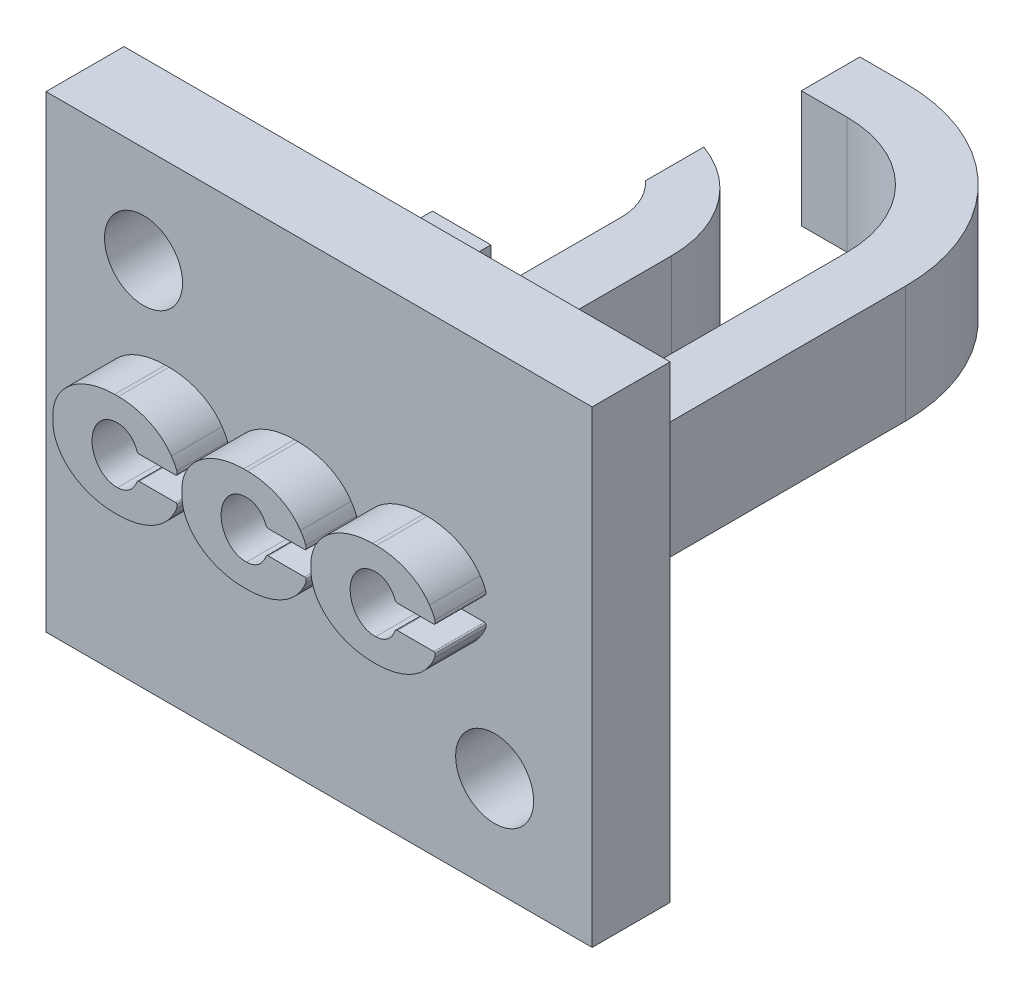
SolidWorks part; units mm, degrees
ref_plane "Front Plane" through (0, 0, 0) normal (0, 0, 1) x (1, 0, 0)
ref_plane "Top Plane" through (0, 0, 0) normal (0, 1, 0) x (1, 0, 0)
ref_plane "Right Plane" through (0, 0, 0) normal (1, 0, 0) x (0, 0, -1)
sketch "Sketch1" plane through (0, 0, 0) normal (0, 0, 1) x (1, 0, 0)
  line L1 (-7.5, 6) -> (7.5, 6)
  line L2 (-7.5, 6) -> (-7.5, -6)
  line L3 (-7.5, -6) -> (7.5, -6)
  line L4 (7.5, 6) -> (7.5, -6)
  line L5 (-7.5, 6) -> (7.5, -6) construction
  line L6 (-7.5, -6) -> (7.5, 6) construction
  point P0 (0, 0)
  dimension "D1" = 15
  dimension "D2" = 12
extrude "Boss-Extrude1" add sketch "Sketch1" along normal blind 2
sketch "Sketch2" plane through (0, 0, 2) normal (0, 0, 1) x (1, 0, 0)
  line L0 (-0.5005, 0.4472) -> (0.4353, 0.4472)
  line L1 (-1.0379, 1.458) -> (-1.1315, 1.458)
  line L2 (-2.7171, 0.2068) -> (-2.7171, 0.0767)
  line L3 (-1.1315, -1.1745) -> (-1.0379, -1.1745)
  line L4 (0.4308, -0.1598) -> (-0.5005, -0.1598)
  line L5 (-3.8088, 0.4472) -> (-2.873, 0.4472)
  line L6 (-4.3462, 1.458) -> (-4.4398, 1.458)
  line L7 (-6.0254, 0.2068) -> (-6.0254, 0.0767)
  line L8 (-4.4398, -1.1745) -> (-4.3462, -1.1745)
  line L9 (-2.8775, -0.1598) -> (-3.8088, -0.1598)
  line L10 (2.8078, 0.4472) -> (3.7437, 0.4472)
  line L11 (2.2704, 1.458) -> (2.1768, 1.458)
  line L12 (0.5912, 0.2068) -> (0.5912, 0.0767)
  line L13 (2.1768, -1.1745) -> (2.2704, -1.1745)
  line L14 (3.7391, -0.1598) -> (2.8078, -0.1598)
  arc A0 (-0.5622, 0.4908) -> (-0.5005, 0.4472) centre (-0.5005, 0.5126) ccw
  arc A1 (0.4353, 0.4472) -> (0.4646, 0.4721) centre (0.4309, 0.4821) ccw
  arc A2 (0.4646, 0.4721) -> (0.4604, 0.5595) centre (0.284, 0.5073) ccw
  arc A3 (0.4604, 0.5595) -> (0.3232, 0.8168) centre (-0.6216, 0.148) ccw
  arc A4 (0.3232, -0.5333) -> (0.4557, -0.287) centre (-0.6122, 0.1283) ccw
  arc A5 (0.4557, -0.287) -> (0.4655, -0.189) centre (0.2842, -0.2203) ccw
  arc A6 (0.4655, -0.189) -> (0.4308, -0.1598) centre (0.4308, -0.195) ccw
  arc A7 (-0.5005, -0.1598) -> (-0.5622, -0.2034) centre (-0.5005, -0.2253) ccw
  arc A8 (-3.8705, 0.4908) -> (-3.8088, 0.4472) centre (-3.8088, 0.5126) ccw
  arc A9 (-2.873, 0.4472) -> (-2.8437, 0.4721) centre (-2.8774, 0.4821) ccw
  arc A10 (-2.8437, 0.4721) -> (-2.8479, 0.5595) centre (-3.0243, 0.5073) ccw
  arc A11 (-2.8479, 0.5595) -> (-2.9851, 0.8168) centre (-3.9299, 0.148) ccw
  arc A12 (-2.9851, -0.5333) -> (-2.8527, -0.287) centre (-3.9205, 0.1283) ccw
  arc A13 (-2.8527, -0.287) -> (-2.8428, -0.189) centre (-3.0241, -0.2203) ccw
  arc A14 (-2.8428, -0.189) -> (-2.8775, -0.1598) centre (-2.8775, -0.195) ccw
  arc A15 (-3.8088, -0.1598) -> (-3.8705, -0.2034) centre (-3.8088, -0.2253) ccw
  arc A16 (2.7461, 0.4908) -> (2.8078, 0.4472) centre (2.8078, 0.5126) ccw
  arc A17 (3.7437, 0.4472) -> (3.7729, 0.4721) centre (3.7392, 0.4821) ccw
  arc A18 (3.7729, 0.4721) -> (3.7687, 0.5595) centre (3.5923, 0.5073) ccw
  arc A19 (3.7687, 0.5595) -> (3.6315, 0.8168) centre (2.6867, 0.148) ccw
  arc A20 (3.6315, -0.5333) -> (3.764, -0.287) centre (2.6961, 0.1283) ccw
  arc A21 (3.764, -0.287) -> (3.7738, -0.189) centre (3.5925, -0.2203) ccw
  arc A22 (3.7738, -0.189) -> (3.7391, -0.1598) centre (3.7391, -0.195) ccw
  arc A23 (2.8078, -0.1598) -> (2.7461, -0.2034) centre (2.8078, -0.2253) ccw
  ellipse E0 centre (-1.0904, 0.1419) end of major axis (-1.0868, -0.5752) minor radius 0.6209 (-1.1185, 0.8583) -> (-1.0587, -0.5743) ccw
  ellipse E1 centre (-1.1465, 0.1419) end of major axis (-1.4291, -0.5397) minor radius 0.6039 (-0.5622, 0.4908) -> (-1.1185, 0.8583) ccw
  ellipse E2 centre (-1.1599, 0.1563) end of major axis (0.4829, 0.4015) minor radius 1.2925 (0.3232, 0.8168) -> (-1.0379, 1.458) ccw
  ellipse E3 centre (-1.0691, 0.1576) end of major axis (-2.714, 0.287) minor radius 1.2979 (-1.1315, 1.458) -> (-2.7171, 0.2068) ccw
  ellipse E4 centre (-1.0691, 0.1259) end of major axis (0.5758, 0.2553) minor radius 1.2979 (-2.7171, 0.0767) -> (-1.1315, -1.1745) ccw
  ellipse E5 centre (-1.1599, 0.1272) end of major axis (-2.8027, 0.3723) minor radius 1.2925 (-1.0379, -1.1745) -> (0.3232, -0.5333) ccw
  ellipse E6 centre (-1.1465, 0.1455) end of major axis (-0.8639, -0.5361) minor radius 0.6039 (-1.0587, -0.5743) -> (-0.5622, -0.2034) ccw
  ellipse E7 centre (-4.4548, 0.1419) end of major axis (-4.1722, 0.8235) minor radius 0.6039 (-3.8705, 0.4908) -> (-4.4268, 0.8583) ccw
  ellipse E8 centre (-4.4682, 0.1563) end of major axis (-2.8254, 0.4015) minor radius 1.2925 (-2.9851, 0.8168) -> (-4.3462, 1.458) ccw
  ellipse E9 centre (-4.3774, 0.1576) end of major axis (-6.0223, 0.287) minor radius 1.2979 (-4.4398, 1.458) -> (-6.0254, 0.2068) ccw
  ellipse E10 centre (-4.3774, 0.1259) end of major axis (-6.0223, -0.0034) minor radius 1.2979 (-6.0254, 0.0767) -> (-4.4398, -1.1745) ccw
  ellipse E11 centre (-4.4682, 0.1272) end of major axis (-6.111, 0.3723) minor radius 1.2925 (-4.3462, -1.1745) -> (-2.9851, -0.5333) ccw
  ellipse E12 centre (-4.4548, 0.1455) end of major axis (-4.7375, 0.8271) minor radius 0.6039 (-4.367, -0.5743) -> (-3.8705, -0.2034) ccw
  ellipse E13 centre (-4.3987, 0.1419) end of major axis (-4.3951, -0.5752) minor radius 0.6209 (-4.4268, 0.8583) -> (-4.367, -0.5743) ccw
  ellipse E14 centre (2.2179, 0.1419) end of major axis (2.2143, 0.859) minor radius 0.6209 (2.1899, 0.8583) -> (2.2496, -0.5743) ccw
  ellipse E15 centre (2.1618, 0.1419) end of major axis (1.8792, -0.5397) minor radius 0.6039 (2.7461, 0.4908) -> (2.1899, 0.8583) ccw
  ellipse E16 centre (2.1484, 0.1563) end of major axis (3.7912, 0.4015) minor radius 1.2925 (3.6315, 0.8168) -> (2.2704, 1.458) ccw
  ellipse E17 centre (2.2392, 0.1576) end of major axis (0.5943, 0.287) minor radius 1.2979 (2.1768, 1.458) -> (0.5912, 0.2068) ccw
  ellipse E18 centre (2.2392, 0.1259) end of major axis (3.8841, 0.2553) minor radius 1.2979 (0.5912, 0.0767) -> (2.1768, -1.1745) ccw
  ellipse E19 centre (2.1484, 0.1272) end of major axis (0.5056, 0.3723) minor radius 1.2925 (2.2704, -1.1745) -> (3.6315, -0.5333) ccw
  ellipse E20 centre (2.1618, 0.1455) end of major axis (1.8792, 0.8271) minor radius 0.6039 (2.2496, -0.5743) -> (2.7461, -0.2034) ccw
extrude "Boss-Extrude2" add sketch "Sketch2" along normal blind 2
sketch "Sketch3" plane through (0, 0, 0) normal (0, 1, 0) x (1, 0, 0)
  line L0 (7.5, 0) -> (-7.5, 0) construction
  line L1 (1.8337, 0) -> (3.3337, 0)
  line L2 (1.8337, 0) -> (1.8337, 12.2)
  line L3 (-3.644, -2) -> (-3.644, 5.3789) construction
  line L4 (3.3337, 0) -> (3.3337, 13.7)
  line L5 (-4.394, 0) -> (-2.894, 0)
  line L6 (-4.394, 0) -> (-4.394, 4.8)
  line L7 (-1.0877, -2) -> (-1.0877, 4.6797) construction
  line L8 (-2.894, 0) -> (-2.894, 4.8)
  line L9 (-2.894, 4.8) -> (-4.394, 4.8)
  line L10 (-1.8377, 0) -> (-0.3377, 0)
  line L11 (7.5, -2) -> (-7.5, -2) construction
  line L13 (-1.8377, 0) -> (-1.8377, 8.2)
  line L14 (2.5837, -2) -> (2.5837, 2.787) construction
  line L15 (-0.3377, 0) -> (-0.3377, 9.7)
  line L16 (-0.3377, 9.7) -> (-2.3377, 9.7)
  line L17 (-2.3377, 13.7) -> (3.3337, 13.7)
  line L18 (-1.8377, 8.2) -> (-2.3377, 8.2)
  line L19 (-2.3377, 9.7) -> (-2.3377, 8.2)
  line L20 (-2.3377, 13.7) -> (-2.3377, 12.2)
  line L21 (-2.3377, 12.2) -> (1.8337, 12.2)
  dimension "D1" = 1.5
  dimension "D2" = 4.8
  dimension "D3" = 1.5
  dimension "D4" = 1.5
  dimension "D5" = 8.2
  dimension "D6" = 1.5
  dimension "D7" = 2.5
  dimension "D8" = 1.5
  dimension "D9" = 0.5
  dimension "D10" = 1.0877
  dimension "D11" = 2.5837
  dimension "D12" = 3.644
extrude "Boss-Extrude3" add sketch "Sketch3" along normal mid plane 3
fillet "Fillet3" radius 1.5 1 edges at (-1.8377, 0, -8.2)
fillet "Fillet4" radius 3 1 edges at (-0.3377, 0, -9.7)
fillet "Fillet5" radius 3 1 edges at (1.8337, 0, -12.2)
fillet "Fillet6" radius 4.5 1 edges at (3.3337, 0, -13.7)
sketch "Sketch4" plane through (7.5, 0, 0) normal (1, 0, 0) x (0, 0, -1)
  line L4 (0, -6) -> (0, 6)
  line L5 (0, 6) -> (-2, 6)
  line L6 (-2, 6) -> (-2, -6)
  line L7 (-2, -6) -> (0, -6)
  line L8 (0, -6) -> (0, 6)
  line L9 (0, 6) -> (-2, 6)
  line L10 (-2, 6) -> (-2, -6)
  line L11 (-2, -6) -> (0, -6)
  dimension "D1" = 0
extrude "Cut-Extrude1" cut sketch "Sketch4" against normal blind 1
sketch "Sketch5" plane through (0, 0, 0) normal (0, 0, -1) x (-1, 0, 0)
  line L0 (-6.5, -6) -> (-6.5, 6) construction
  line L1 (7.5, -6) -> (-6.5, -6) construction
  line L2 (7.5, 6) -> (7.5, -6) construction
  line L3 (-6.5, 6) -> (7.5, 6) construction
  circle A0 centre (-4, -3.5) radius 1
  circle A1 centre (5, 3.5) radius 1
  dimension "D1" = 2
  dimension "D2" = 2.5
  dimension "D3" = 2.5
  dimension "D4" = 2.5
  dimension "D5" = 2.5
extrude "Cut-Extrude2" cut sketch "Sketch5" against normal through all
sketch "Sketch6" plane through (0, 0, 4) normal (0, 0, 1) x (1, 0, 0)
  line L0 (-0.5005, 0.4472) -> (0.4353, 0.4472) construction
  line L1 (-1.0379, 1.458) -> (-1.1315, 1.458) construction
  line L2 (-2.7171, 0.2068) -> (-2.7171, 0.0767) construction
  line L3 (-1.1315, -1.1745) -> (-1.0379, -1.1745) construction
  line L4 (0.4308, -0.1598) -> (-0.5005, -0.1598) construction
  line L5 (-3.8088, 0.4472) -> (-2.873, 0.4472)
  line L6 (-4.3462, 1.458) -> (-4.4398, 1.458)
  line L7 (-6.0254, 0.2068) -> (-6.0254, 0.0767)
  line L8 (-4.4398, -1.1745) -> (-4.3462, -1.1745)
  line L9 (-2.8775, -0.1598) -> (-3.8088, -0.1598)
  line L10 (-3.8088, 0.4472) -> (-2.873, 0.4472)
  line L11 (-4.3462, 1.458) -> (-4.4398, 1.458)
  line L12 (-6.0254, 0.2068) -> (-6.0254, 0.0767)
  line L13 (-4.4398, -1.1745) -> (-4.3462, -1.1745)
  line L14 (-2.8775, -0.1598) -> (-3.8088, -0.1598)
  line L15 (2.8078, 0.4472) -> (3.7437, 0.4472) construction
  line L16 (2.2704, 1.458) -> (2.1768, 1.458) construction
  line L17 (0.5912, 0.2068) -> (0.5912, 0.0767) construction
  line L18 (2.1768, -1.1745) -> (2.2704, -1.1745) construction
  line L19 (3.7391, -0.1598) -> (2.8078, -0.1598) construction
  line L20 (-0.5005, 0.4472) -> (0.4353, 0.4472)
  line L21 (-1.0379, 1.458) -> (-1.1315, 1.458)
  line L22 (-2.7171, 0.2068) -> (-2.7171, 0.0767)
  line L23 (-1.1315, -1.1745) -> (-1.0379, -1.1745)
  line L24 (0.4308, -0.1598) -> (-0.5005, -0.1598)
  line L25 (2.8078, 0.4472) -> (3.7437, 0.4472)
  line L26 (2.2704, 1.458) -> (2.1768, 1.458)
  line L27 (0.5912, 0.2068) -> (0.5912, 0.0767)
  line L28 (2.1768, -1.1745) -> (2.2704, -1.1745)
  line L29 (3.7391, -0.1598) -> (2.8078, -0.1598)
  arc A0 (-0.5622, 0.4908) -> (-0.5005, 0.4472) centre (-0.5005, 0.5126) ccw construction
  arc A1 (0.4353, 0.4472) -> (0.4646, 0.4721) centre (0.4309, 0.4821) ccw construction
  arc A2 (0.4646, 0.4721) -> (0.4604, 0.5595) centre (0.284, 0.5073) ccw construction
  arc A3 (0.4604, 0.5595) -> (0.3232, 0.8168) centre (-0.6216, 0.148) ccw construction
  arc A4 (0.3232, -0.5333) -> (0.4557, -0.287) centre (-0.6122, 0.1283) ccw construction
  arc A5 (0.4557, -0.287) -> (0.4655, -0.189) centre (0.2842, -0.2203) ccw construction
  arc A6 (0.4655, -0.189) -> (0.4308, -0.1598) centre (0.4308, -0.195) ccw construction
  arc A7 (-0.5005, -0.1598) -> (-0.5622, -0.2034) centre (-0.5005, -0.2253) ccw construction
  arc A8 (-3.8705, 0.4908) -> (-3.8088, 0.4472) centre (-3.8088, 0.5126) ccw
  arc A9 (-2.873, 0.4472) -> (-2.8437, 0.4721) centre (-2.8774, 0.4821) ccw
  arc A10 (-2.8437, 0.4721) -> (-2.8479, 0.5595) centre (-3.0243, 0.5073) ccw
  arc A11 (-2.8479, 0.5595) -> (-2.9851, 0.8168) centre (-3.9299, 0.148) ccw
  arc A12 (-2.9851, -0.5333) -> (-2.8527, -0.287) centre (-3.9205, 0.1283) ccw
  arc A13 (-2.8527, -0.287) -> (-2.8428, -0.189) centre (-3.0241, -0.2203) ccw
  arc A14 (-2.8428, -0.189) -> (-2.8775, -0.1598) centre (-2.8775, -0.195) ccw
  arc A15 (-3.8088, -0.1598) -> (-3.8705, -0.2034) centre (-3.8088, -0.2253) ccw
  arc A16 (-3.8705, 0.4908) -> (-3.8088, 0.4472) centre (-3.8088, 0.5126) ccw
  arc A17 (-2.873, 0.4472) -> (-2.8437, 0.4721) centre (-2.8774, 0.4821) ccw
  arc A18 (-2.8437, 0.4721) -> (-2.8479, 0.5595) centre (-3.0243, 0.5073) ccw
  arc A19 (-2.8479, 0.5595) -> (-2.9851, 0.8168) centre (-3.9299, 0.148) ccw
  arc A20 (-2.9851, -0.5333) -> (-2.8527, -0.287) centre (-3.9205, 0.1283) ccw
  arc A21 (-2.8527, -0.287) -> (-2.8428, -0.189) centre (-3.0241, -0.2203) ccw
  arc A22 (-2.8428, -0.189) -> (-2.8775, -0.1598) centre (-2.8775, -0.195) ccw
  arc A23 (-3.8088, -0.1598) -> (-3.8705, -0.2034) centre (-3.8088, -0.2253) ccw
  arc A24 (2.7461, 0.4908) -> (2.8078, 0.4472) centre (2.8078, 0.5126) ccw construction
  arc A25 (3.7437, 0.4472) -> (3.7729, 0.4721) centre (3.7392, 0.4821) ccw construction
  arc A26 (3.7729, 0.4721) -> (3.7687, 0.5595) centre (3.5923, 0.5073) ccw construction
  arc A27 (3.7687, 0.5595) -> (3.6315, 0.8168) centre (2.6867, 0.148) ccw construction
  arc A28 (3.6315, -0.5333) -> (3.764, -0.287) centre (2.6961, 0.1283) ccw construction
  arc A29 (3.764, -0.287) -> (3.7738, -0.189) centre (3.5925, -0.2203) ccw construction
  arc A30 (3.7738, -0.189) -> (3.7391, -0.1598) centre (3.7391, -0.195) ccw construction
  arc A31 (2.8078, -0.1598) -> (2.7461, -0.2034) centre (2.8078, -0.2253) ccw construction
  arc A32 (-0.5622, 0.4908) -> (-0.5005, 0.4472) centre (-0.5005, 0.5126) ccw
  arc A33 (0.4353, 0.4472) -> (0.4646, 0.4721) centre (0.4309, 0.4821) ccw
  arc A34 (0.4646, 0.4721) -> (0.4604, 0.5595) centre (0.284, 0.5073) ccw
  arc A35 (0.4604, 0.5595) -> (0.3232, 0.8168) centre (-0.6216, 0.148) ccw
  arc A36 (0.3232, -0.5333) -> (0.4557, -0.287) centre (-0.6122, 0.1283) ccw
  arc A37 (0.4557, -0.287) -> (0.4655, -0.189) centre (0.2842, -0.2203) ccw
  arc A38 (0.4655, -0.189) -> (0.4308, -0.1598) centre (0.4308, -0.195) ccw
  arc A39 (-0.5005, -0.1598) -> (-0.5622, -0.2034) centre (-0.5005, -0.2253) ccw
  arc A40 (2.7461, 0.4908) -> (2.8078, 0.4472) centre (2.8078, 0.5126) ccw
  arc A41 (3.7437, 0.4472) -> (3.7729, 0.4721) centre (3.7392, 0.4821) ccw
  arc A42 (3.7729, 0.4721) -> (3.7687, 0.5595) centre (3.5923, 0.5073) ccw
  arc A43 (3.7687, 0.5595) -> (3.6315, 0.8168) centre (2.6867, 0.148) ccw
  arc A44 (3.6315, -0.5333) -> (3.764, -0.287) centre (2.6961, 0.1283) ccw
  arc A45 (3.764, -0.287) -> (3.7738, -0.189) centre (3.5925, -0.2203) ccw
  arc A46 (3.7738, -0.189) -> (3.7391, -0.1598) centre (3.7391, -0.195) ccw
  arc A47 (2.8078, -0.1598) -> (2.7461, -0.2034) centre (2.8078, -0.2253) ccw
  ellipse E0 centre (-1.1465, 0.1419) end of major axis (-0.8639, 0.8235) minor radius 0.6039 (-0.5622, 0.4908) -> (-1.1185, 0.8583) ccw construction
  ellipse E1 centre (-1.1599, 0.1563) end of major axis (0.4829, 0.4015) minor radius 1.2925 (0.3232, 0.8168) -> (-1.0379, 1.458) ccw construction
  ellipse E2 centre (-1.0691, 0.1576) end of major axis (-2.714, 0.287) minor radius 1.2979 (-1.1315, 1.458) -> (-2.7171, 0.2068) ccw construction
  ellipse E3 centre (-1.0691, 0.1259) end of major axis (0.5758, 0.2553) minor radius 1.2979 (-2.7171, 0.0767) -> (-1.1315, -1.1745) ccw construction
  ellipse E4 centre (-1.1599, 0.1272) end of major axis (-2.8027, 0.3723) minor radius 1.2925 (-1.0379, -1.1745) -> (0.3232, -0.5333) ccw construction
  ellipse E5 centre (-1.1465, 0.1455) end of major axis (-0.8639, -0.5361) minor radius 0.6039 (-1.0587, -0.5743) -> (-0.5622, -0.2034) ccw construction
  ellipse E6 centre (-1.0904, 0.1419) end of major axis (-1.0868, -0.5752) minor radius 0.6209 (-1.1185, 0.8583) -> (-1.0587, -0.5743) ccw construction
  ellipse E7 centre (-4.4548, 0.1419) end of major axis (-4.7375, -0.5397) minor radius 0.6039 (-3.8705, 0.4908) -> (-4.4268, 0.8583) ccw
  ellipse E8 centre (-4.4682, 0.1563) end of major axis (-2.8254, 0.4015) minor radius 1.2925 (-2.9851, 0.8168) -> (-4.3462, 1.458) ccw
  ellipse E9 centre (-4.3774, 0.1576) end of major axis (-6.0223, 0.287) minor radius 1.2979 (-4.4398, 1.458) -> (-6.0254, 0.2068) ccw
  ellipse E10 centre (-4.3774, 0.1259) end of major axis (-6.0223, -0.0034) minor radius 1.2979 (-6.0254, 0.0767) -> (-4.4398, -1.1745) ccw
  ellipse E11 centre (-4.4682, 0.1272) end of major axis (-6.111, 0.3723) minor radius 1.2925 (-4.3462, -1.1745) -> (-2.9851, -0.5333) ccw
  ellipse E12 centre (-4.4548, 0.1455) end of major axis (-4.1722, -0.5361) minor radius 0.6039 (-4.367, -0.5743) -> (-3.8705, -0.2034) ccw
  ellipse E13 centre (-4.3987, 0.1419) end of major axis (-4.3951, -0.5752) minor radius 0.6209 (-4.4268, 0.8583) -> (-4.367, -0.5743) ccw
  ellipse E14 centre (-4.4548, 0.1419) end of major axis (-4.7375, -0.5397) minor radius 0.6039 (-3.8705, 0.4908) -> (-4.4268, 0.8583) ccw
  ellipse E15 centre (-4.4682, 0.1563) end of major axis (-2.8254, 0.4015) minor radius 1.2925 (-2.9851, 0.8168) -> (-4.3462, 1.458) ccw
  ellipse E16 centre (-4.3774, 0.1576) end of major axis (-6.0223, 0.287) minor radius 1.2979 (-4.4398, 1.458) -> (-6.0254, 0.2068) ccw
  ellipse E17 centre (-4.3774, 0.1259) end of major axis (-6.0223, -0.0034) minor radius 1.2979 (-6.0254, 0.0767) -> (-4.4398, -1.1745) ccw
  ellipse E18 centre (-4.4682, 0.1272) end of major axis (-6.111, 0.3723) minor radius 1.2925 (-4.3462, -1.1745) -> (-2.9851, -0.5333) ccw
  ellipse E19 centre (-4.4548, 0.1455) end of major axis (-4.1722, -0.5361) minor radius 0.6039 (-4.367, -0.5743) -> (-3.8705, -0.2034) ccw
  ellipse E20 centre (-4.3987, 0.1419) end of major axis (-4.3951, -0.5752) minor radius 0.6209 (-4.4268, 0.8583) -> (-4.367, -0.5743) ccw
  ellipse E21 centre (2.1618, 0.1419) end of major axis (1.8792, -0.5397) minor radius 0.6039 (2.7461, 0.4908) -> (2.1899, 0.8583) ccw construction
  ellipse E22 centre (2.1484, 0.1563) end of major axis (3.7912, 0.4015) minor radius 1.2925 (3.6315, 0.8168) -> (2.2704, 1.458) ccw construction
  ellipse E23 centre (2.2392, 0.1576) end of major axis (0.5943, 0.287) minor radius 1.2979 (2.1768, 1.458) -> (0.5912, 0.2068) ccw construction
  ellipse E24 centre (2.2392, 0.1259) end of major axis (3.8841, 0.2553) minor radius 1.2979 (0.5912, 0.0767) -> (2.1768, -1.1745) ccw construction
  ellipse E25 centre (2.1484, 0.1272) end of major axis (0.5056, 0.3723) minor radius 1.2925 (2.2704, -1.1745) -> (3.6315, -0.5333) ccw construction
  ellipse E26 centre (2.1618, 0.1455) end of major axis (2.4444, -0.5361) minor radius 0.6039 (2.2496, -0.5743) -> (2.7461, -0.2034) ccw construction
  ellipse E27 centre (2.2179, 0.1419) end of major axis (2.2215, -0.5752) minor radius 0.6209 (2.1899, 0.8583) -> (2.2496, -0.5743) ccw construction
  ellipse E28 centre (-1.1465, 0.1419) end of major axis (-1.4291, -0.5397) minor radius 0.6039 (-0.5622, 0.4908) -> (-1.1185, 0.8583) ccw
  ellipse E29 centre (-1.1599, 0.1563) end of major axis (0.4829, 0.4015) minor radius 1.2925 (0.3232, 0.8168) -> (-1.0379, 1.458) ccw
  ellipse E30 centre (-1.0691, 0.1576) end of major axis (-2.714, 0.287) minor radius 1.2979 (-1.1315, 1.458) -> (-2.7171, 0.2068) ccw
  ellipse E31 centre (-1.0691, 0.1259) end of major axis (0.5758, 0.2553) minor radius 1.2979 (-2.7171, 0.0767) -> (-1.1315, -1.1745) ccw
  ellipse E32 centre (-1.1599, 0.1272) end of major axis (-2.8027, 0.3723) minor radius 1.2925 (-1.0379, -1.1745) -> (0.3232, -0.5333) ccw
  ellipse E33 centre (-1.1465, 0.1455) end of major axis (-0.8639, -0.5361) minor radius 0.6039 (-1.0587, -0.5743) -> (-0.5622, -0.2034) ccw
  ellipse E34 centre (-1.0904, 0.1419) end of major axis (-1.0868, -0.5752) minor radius 0.6209 (-1.1185, 0.8583) -> (-1.0587, -0.5743) ccw
  ellipse E35 centre (2.1618, 0.1419) end of major axis (1.8792, -0.5397) minor radius 0.6039 (2.7461, 0.4908) -> (2.1899, 0.8583) ccw
  ellipse E36 centre (2.1484, 0.1563) end of major axis (3.7912, 0.4015) minor radius 1.2925 (3.6315, 0.8168) -> (2.2704, 1.458) ccw
  ellipse E37 centre (2.2392, 0.1576) end of major axis (0.5943, 0.287) minor radius 1.2979 (2.1768, 1.458) -> (0.5912, 0.2068) ccw
  ellipse E38 centre (2.2392, 0.1259) end of major axis (3.8841, 0.2553) minor radius 1.2979 (0.5912, 0.0767) -> (2.1768, -1.1745) ccw
  ellipse E39 centre (2.1484, 0.1272) end of major axis (0.5056, 0.3723) minor radius 1.2925 (2.2704, -1.1745) -> (3.6315, -0.5333) ccw
  ellipse E40 centre (2.1618, 0.1455) end of major axis (2.4444, -0.5361) minor radius 0.6039 (2.2496, -0.5743) -> (2.7461, -0.2034) ccw
  ellipse E41 centre (2.2179, 0.1419) end of major axis (2.2215, -0.5752) minor radius 0.6209 (2.1899, 0.8583) -> (2.2496, -0.5743) ccw
  dimension "D1" = 0
extrude "Cut-Extrude3" cut sketch "Sketch6" against normal blind 0.7
